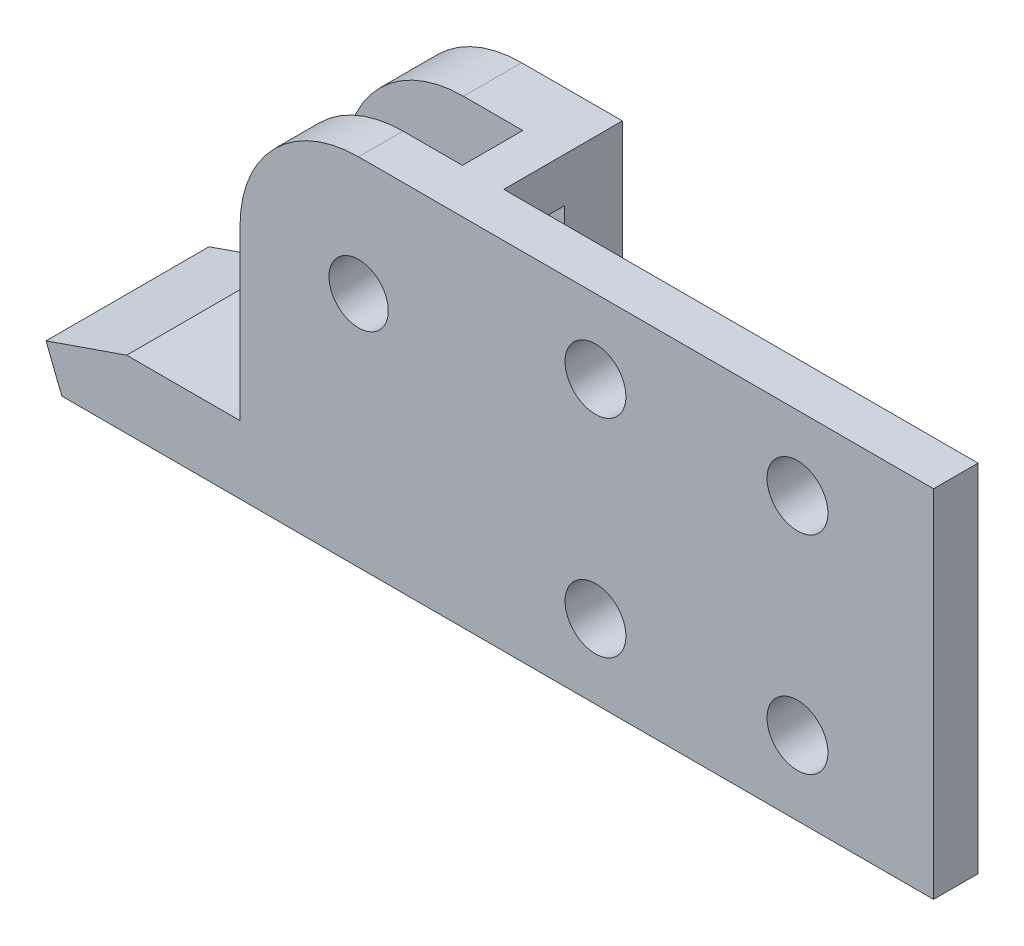
SolidWorks part; units mm, degrees
note: The reader was unsure of these and kept them because the rebuilt part matched: shared geometry of "Sketch12<3>".
ref_plane "Front Plane" through (0, 0, 0) normal (0, 0, 1) x (1, 0, 0)
ref_plane "Top Plane" through (0, 0, 0) normal (0, 1, 0) x (1, 0, 0)
ref_plane "Right Plane" through (0, 0, 0) normal (1, 0, 0) x (0, 0, -1)
sketch "Sketch2" plane through (0, 0, 0) normal (0, 0, 1) x (1, 0, 0)
  line L0 (-36.2055, -212.6584) -> (-69.6869, -224.2524) construction
  line L4 (25.4, -305.6274) -> (25.4, 320.675) construction
  line L7 (-67.9862, -228.5334) -> (-69.6869, -224.2524)
  line L8 (-48.895, -221.2606) -> (-48.895, -203.1334)
  line L10 (-36.195, -190.4334) -> (25.4, -190.4334)
  line L13 (-69.6869, -224.2524) -> (-61.047, -221.2606)
  line L15 (25.4, -190.4334) -> (25.4, -228.5334)
  line L16 (25.4, -228.5334) -> (-67.9862, -228.5334)
  line L17 (-61.047, -221.2606) -> (-48.895, -221.2606)
  line L18 (-25.4, -190.4334) -> (-25.4, -228.5334) construction
  circle A0 centre (-36.195, -203.1334) radius 3.175
  circle A1 centre (-36.195, -203.1334) radius 39.5944 construction
  arc A2 (-74.6371, -212.6159) -> (-69.6869, -224.2524) centre (-36.195, -203.1334) ccw construction
  arc A4 (-36.195, -190.4334) -> (-48.895, -203.1334) centre (-36.195, -203.1334) ccw
  point P16 (-48.895, -217.0525)
  dimension "D1" = 12.7
  dimension "D2" = 79.1888
  dimension "D3" = 50.8
  dimension "D4" = 4.208
extrude "Boss-Extrude1" add sketch "Sketch2" along normal blind 4.7625
sketch "Sketch4" plane through (61.8785, -178.6935, 0) normal (-0.3272, 0.9449, 0) x (0.9449, 0.3272, 0)
  line L1 (-95.8313, 4.7625) -> (-140.1004, 4.7625) construction
  line L2 (-136.6903, 4.7625) -> (-136.6903, 2.3812) construction
  line L3 (-136.6903, 4.7625) -> (-139.2303, 4.7625) construction
  line L4 (-139.2303, -4.7625) -> (-139.2303, 0) construction
  dimension "D1" = 2.54
hole_wizard "3/16 (0.1875) Diameter Hole1" [suppressed] positions "Sketch9" profile "Sketch10" hole size "3/16" standard "ANSI Inch"
sketch "Sketch9" plane through (61.8785, -178.6935, 0) normal (-0.3272, 0.9449, 0) x (0.9449, 0.3272, 0)
  point P0 (-136.6903, 2.3812)
sketch "Sketch10" plane through (-67.2867, -223.4212, -2.3812) normal (0, 0, 1) x (-0.9449, -0.3272, 0)
  line L0 (0, 0) -> (0, 3.9708)
  line L1 (0, 3.9708) -> (2.3812, 2.54)
  line L2 (2.3812, 2.54) -> (2.3812, 0)
  line L5 (2.3812, 0) -> (0, 0)
  line L10 (0, 3.9708) -> (-2.3812, 2.54) construction
  line L11 (0, -6.35) -> (0, 107.95) construction
  dimension "Hole Dia." = 4.7625
  dimension "Hole Depth" = 2.54
  dimension "Drill Angle" = 118
sketch "Sketch11" plane through (0, 0, 0) normal (0, 0, -1) x (-1, 0, 0)
  line L0 (-25.4, -190.4334) -> (25.4, -190.4334) construction
  line L1 (-25.4, -190.4334) -> (36.195, -190.4334) construction
  line L2 (25.4, -190.4334) -> (25.4, -228.5334)
  line L3 (67.9862, -228.5334) -> (-25.4, -228.5334) construction
  line L4 (25.4, -228.5334) -> (67.9862, -228.5334)
  line L5 (67.9862, -228.5334) -> (69.6869, -224.2524)
  line L6 (69.6869, -224.2524) -> (61.047, -221.2606)
  line L7 (61.047, -221.2606) -> (48.895, -221.2606)
  line L8 (48.895, -221.2606) -> (48.895, -203.1334)
  line L9 (36.195, -190.4334) -> (25.4, -190.4334)
  arc A0 (48.895, -203.1334) -> (36.195, -190.4334) centre (36.195, -203.1334) ccw
  arc A1 (48.895, -203.1334) -> (36.195, -190.4334) centre (36.195, -203.1334) ccw construction
extrude "Boss-Extrude2" add sketch "Sketch11" along normal blind 12.7
sketch "Sketch12" plane through (-48.895, 0, 0) normal (-1, 0, 0) x (0, 0, 1)
  line L0 (0, -221.2606) -> (0, -217.0525) construction
  line L1 (0, -190.4334) -> (0, -228.5334) construction
  line L2 (0, -190.4334) -> (0, -228.5334) construction
  line L3 (0, -217.0525) -> (0, -190.4334)
  line L4 (0, -190.4334) -> (-6.477, -190.4334)
  line L5 (4.7625, -190.4334) -> (-12.7, -190.4334) construction
  line L6 (-6.477, -190.4334) -> (-6.477, -217.0525)
  line L7 (-6.477, -217.0525) -> (0, -217.0525)
  line L8 (0, -195.1959) -> (-6.477, -195.1959)
  line M6 (4.7625, -203.1334) -> (-12.7, -203.1334)
  dimension "D1" = 4.7625
  dimension "D2" = 6.477
extrude "Cut-Extrude1" cut sketch "Sketch12" against normal blind 24.13 contours L6 L7 L3 M6 | L3 L8 L6 M6
extrude "Cut-Extrude2" cut sketch "Sketch12<3>" against normal blind 19.05 contours L8 L3 L4 L6
sketch "Sketch12<3>" plane through (-48.895, 0, 0) normal (-1, 0, 0) x (0, 0, 1) same geometry as "Sketch12"
hole_wizard "Tap Drill for #10-32 Tap1" positions "Sketch13" profile "Sketch14" hole size "#10-32" standard "ANSI Inch" end condition through all
sketch "Sketch13" plane through (0, 0, -6.477) normal (0, 0, 1) x (1, 0, 0)
  point P0 (-36.195, -203.1334)
sketch "Sketch14" plane through (-36.195, -203.1334, -6.477) normal (1, 0, 0) x (0, -1, 0)
  line L0 (0, 0) -> (0, 6.223)
  line L1 (0, 6.223) -> (2.0193, 6.223)
  line L2 (2.0193, 6.223) -> (2.0193, 0)
  line L5 (2.0193, 0) -> (0, 0)
  line L11 (0, -6.35) -> (0, 107.95) construction
  dimension "Thru Hole Dia." = 4.0386
  dimension "Thru Hole Depth" = 6.223
sketch "Sketch15" plane through (0, 0, 4.7625) normal (0, 0, 1) x (1, 0, 0)
  line L0 (-25.4, -190.4334) -> (25.4, -228.5334) construction
  line L1 (0, -209.4834) -> (10.8204, -209.4834) construction
  line L2 (0, -209.4834) -> (0, -204.4261) construction
  line L3 (0, -209.4834) -> (-10.8204, -209.4834) construction
  line L4 (10.8204, -209.4834) -> (10.8204, -198.3709) construction
  line L5 (10.8204, -209.4834) -> (10.8204, -220.5959) construction
  line L6 (-10.8204, -209.4834) -> (-10.8204, -198.3709) construction
  line L7 (-10.8204, -209.4834) -> (-10.8204, -220.5959) construction
  dimension "D1" = 21.6408
  dimension "D2" = 22.225
  dimension "D3" = 22.225
hole_wizard "1/4 Clearance Hole1" positions "Sketch16" profile "Sketch17" hole size "1/4" standard "ANSI Inch" end condition through all
sketch "Sketch16" plane through (0, 0, 4.7625) normal (0, 0, 1) x (1, 0, 0)
  point P0 (-10.8204, -198.3709)
  point P3 (-10.8204, -220.5959)
  point P6 (10.8204, -220.5959)
  point P9 (10.8204, -198.3709)
sketch "Sketch17" plane through (-10.8204, -198.3709, 4.7625) normal (1, 0, 0) x (0, -1, 0)
  line L0 (0, 0) -> (0, 17.4625)
  line L1 (0, 17.4625) -> (3.2639, 17.4625)
  line L2 (3.2639, 17.4625) -> (3.2639, 0)
  line L5 (3.2639, 0) -> (0, 0)
  line L11 (0, -6.35) -> (0, 107.95) construction
  dimension "Thru Hole Dia." = 6.5278
  dimension "Thru Hole Depth" = 17.4625
